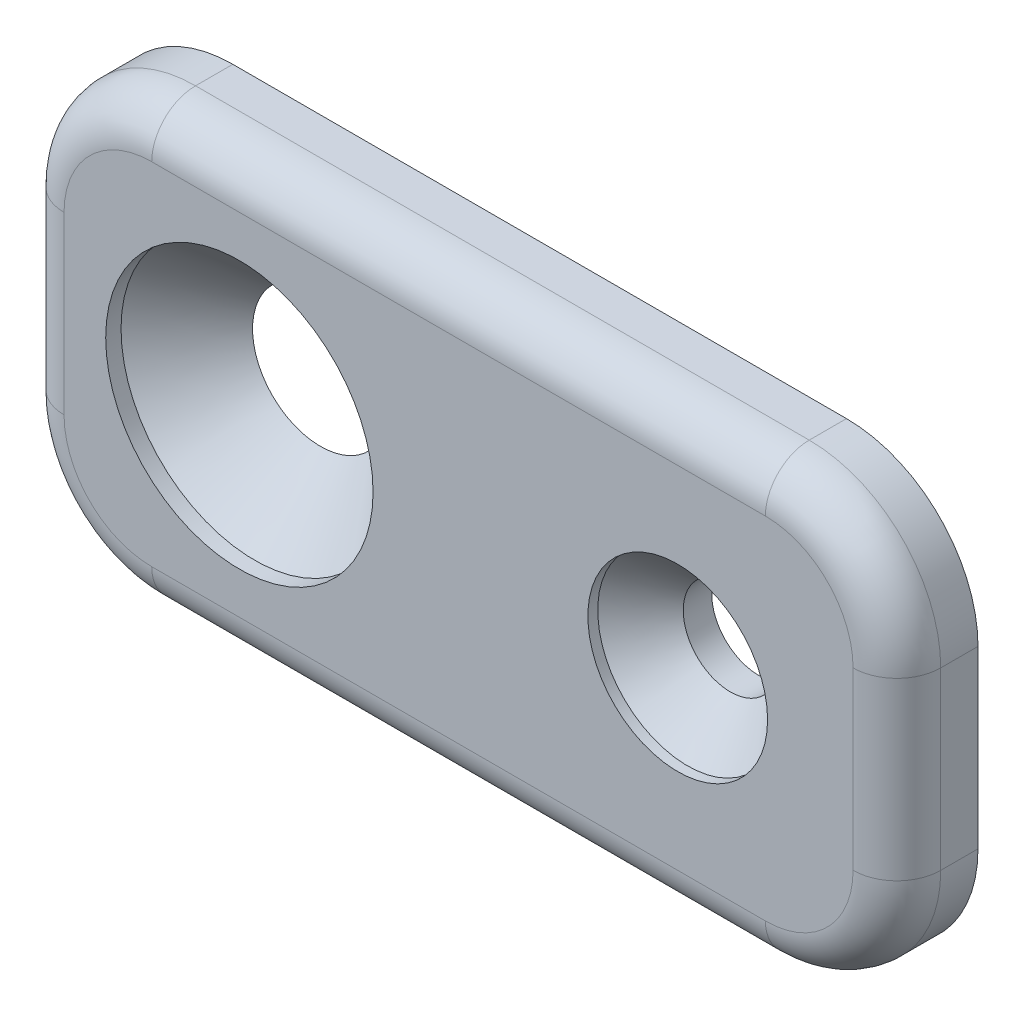
SolidWorks part; units mm, degrees
material "Custom Plastic"
ref_plane "Front Plane" through (0, 0, 0) normal (0, 0, 1) x (1, 0, 0)
ref_plane "Top Plane" through (0, 0, 0) normal (0, 1, 0) x (1, 0, 0)
ref_plane "Right Plane" through (0, 0, 0) normal (1, 0, 0) x (0, 0, -1)
sketch "Sketch1" plane through (0, 0, 0) normal (0, 0, 1) x (1, 0, 0)
  line L1 (30, 10) -> (-10, 10)
  line L2 (30, 10) -> (30, -10)
  line L3 (30, -10) -> (-10, -10)
  line L4 (-10, 10) -> (-10, -10)
  line L5 (30, 10) -> (-10, -10) construction
  line L6 (30, -10) -> (-10, 10) construction
  circle A0 centre (0, 0) radius 3.1
  circle A1 centre (20, 0) radius 2.15
  point P5 (10, 0)
  dimension "D1" = 6.2
  dimension "D4" = 4.3
  dimension "D5" = 20
  dimension "D2" = 10
  dimension "D3" = 20
  dimension "D6" = 40
extrude "Boss-Extrude1" add sketch "Sketch1" along normal blind 3.7
sketch "Sketch2" plane through (0, 0, 3.7) normal (0, 0, 1) x (1, 0, 0)
  circle A0 centre (0, 0) radius 6.1
  dimension "D1" = 12.2
extrude "Cut-Extrude1" cut sketch "Sketch2" against normal blind 0.7
chamfer "Chamfer1" distance 3 angle 45 1 edges at (3.1, 0, 3)
sketch "Sketch3" plane through (0, 0, 3.7) normal (0, 0, 1) x (1, 0, 0)
  circle A0 centre (20, 0) radius 4.1
  dimension "D1" = 8.2
extrude "Cut-Extrude2" cut sketch "Sketch3" against normal blind 0.4
chamfer "Chamfer2" distance 2 angle 45 1 edges at (22.15, 0, 3.3)
fillet "Fillet1" radius 6 4 edges at (30, -10, 1.85) (-10, -10, 1.85) (30, 10, 1.85) (-10, 10, 1.85)
fillet "Fillet2" radius 2 8 edges at (10, -10, 3.7) (28.2426, -8.2426, 3.7) (30, 0, 3.7) (28.2426, 8.2426, 3.7) (10, 10, 3.7) (-8.2426, 8.2426, 3.7) (-10, 0, 3.7) (-8.2426, -8.2426, 3.7)
equation "\"y-cross-rib-thickness\"=6"
equation "\"y-rib-thickness\"=6"
equation "\"bed-plate-thickness\"=6"
equation "\"x-plate-thickness\"=5"
equation "\"rod-diameter\"=12"
equation "\"t-nut-hole-diameter\"=3"
equation "\"y-plate-thickness\"=5"
equation "\"enclosure-thickness\"=0.6"
equation "\"M3-Clearance\"=3.3"
equation "\"M4-Clearance\"=4.3"
equation "\"M5-Clearance\"=5.3"
equation "\"M6-Clearance\"=6.3"
equation "\"M8-Clearance\"=8.3"
equation "\"623-Bearing-Dia\"=11.2"
